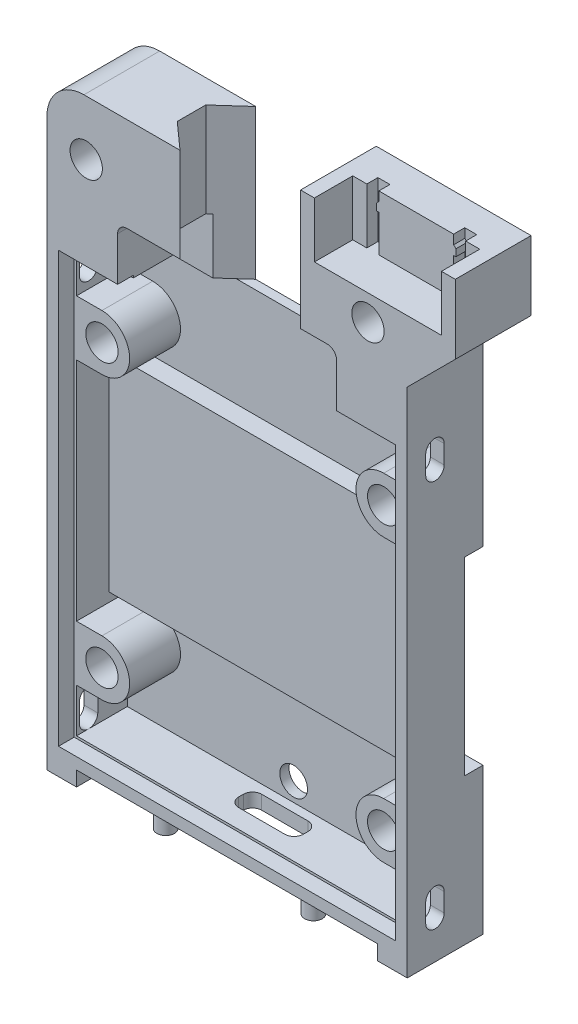
SolidWorks part; units mm, degrees
ref_plane "Front Plane" through (0, 0, 0) normal (0, 0, 1) x (1, 0, 0)
ref_plane "Top Plane" through (0, 0, 0) normal (0, 1, 0) x (1, 0, 0)
ref_plane "Right Plane" through (0, 0, 0) normal (1, 0, 0) x (0, 0, -1)
sketch "Sketch1" plane through (0, 0, 0) normal (0, 0, 1) x (1, 0, 0)
  line L0 (15.25, -20.35) -> (18, -20.35)
  line L1 (-19.5, -32.6) -> (19.5, -32.6)
  line L2 (-19.5, -32.6) -> (-19.5, 31.1)
  line L3 (-19.5, 31.1) -> (19.5, 31.1)
  line L4 (19.5, -32.6) -> (19.5, 31.1)
  line L5 (-15.25, -20.35) -> (-18, -20.35)
  line L6 (15.25, -26.35) -> (18, -26.35)
  line L7 (6.95, 31.1) -> (-15.5, 31.1) construction
  line L8 (-18, -31.1) -> (-18, 29.6)
  line L9 (-18, 29.6) -> (18, 29.6)
  line L10 (18, -31.1) -> (18, 29.6)
  line L11 (-18, -31.1) -> (18, -31.1)
  line L12 (-18, 14.9) -> (18, 14.9)
  line L13 (7.85, 14.9) -> (-4.95, 14.9) construction
  line L14 (-15.25, 4.15) -> (-18, 4.15)
  line L15 (-15.25, 10.15) -> (-18, 10.15)
  line L16 (15.25, 10.15) -> (18, 10.15)
  line L17 (15.25, 4.15) -> (18, 4.15)
  line L18 (-15.25, -26.35) -> (-18, -26.35)
  line L19 (19.5, -34.2) -> (19.5, -18.35) construction
  line L20 (-19.5, -34.2) -> (-19.5, -18.35) construction
  line L21 (15.3, -32.6) -> (-15.3, -32.6) construction
  line L22 (0, 31.1) -> (0, -32.6) construction
  line L23 (9.45, 26.9) -> (24.7, 26.9)
  line L24 (9.45, 26.9) -> (9.45, 33.9)
  line L25 (9.45, 33.9) -> (24.7, 33.9)
  line L26 (24.7, 26.9) -> (24.7, 33.9)
  line L27 (18, 29.6) -> (19.5, 31.1) construction
  line L28 (18.75, 30.35) -> (0, 30.35) construction
  line L29 (9.45, 26.9) -> (7.95, 26.9) construction
  line L30 (-7.95, 31.1) -> (7.95, 31.1)
  line L31 (-7.95, 31.1) -> (-7.95, 29.6)
  line L32 (-7.95, 29.6) -> (7.95, 29.6)
  line L33 (7.95, 31.1) -> (7.95, 29.6)
  line L34 (-7.95, 31.1) -> (7.95, 29.6) construction
  line L35 (-7.95, 29.6) -> (7.95, 31.1) construction
  line L36 (7.95, 26.9) -> (7.95, 29.6) construction
  line L37 (18, 29.6) -> (19.5, 29.6) construction
  line L38 (24.7, 26.4) -> (19.5, 21.2)
  line L39 (9.45, 33.9) -> (7.95, 33.9)
  line L40 (23.2, 33.9) -> (23.2, 26.9)
  line L41 (7.95, 33.9) -> (7.95, 31.1)
  line L42 (24.7, 30.4) -> (23.2, 30.4) construction
  line L43 (24.7, 26.9) -> (19.5, 26.9)
  line L44 (24.7, 26.9) -> (24.7, 26.4)
  line L45 (24.7, 26.4) -> (19.5, 26.4)
  line L46 (19.5, 26.9) -> (19.5, 26.4)
  circle A0 centre (15.25, -23.35) radius 1.75
  arc A1 (-15.5, 31.1) -> (-19.5, 27.1) centre (-15.5, 27.1) ccw construction
  circle A2 centre (15.25, -23.35) radius 3
  arc A3 (-15.5, 31.1) -> (-19.5, 27.1) centre (-15.5, 27.1) ccw
  arc A4 (-15.5, 29.6) -> (-18, 27.1) centre (-15.5, 27.1) ccw
  circle A6 centre (-15.25, -23.35) radius 1.75
  circle A7 centre (-15.25, -23.35) radius 1.75
  circle A8 centre (-15.25, 7.15) radius 1.75
  circle A9 centre (15.25, 7.15) radius 1.75
  circle A10 centre (15.25, 25.15) radius 1.75
  circle A11 centre (-15.25, 25.15) radius 1.75
  circle A12 centre (-15.25, -23.35) radius 3
  circle A13 centre (-15.25, -23.35) radius 3
  circle A14 centre (15.25, 7.15) radius 3
  circle A15 centre (-15.25, 7.15) radius 3
  dimension "D2" = 1.5
  dimension "D4" = 6
  dimension "D3" = 3.5
  dimension "D5" = 13.75
  dimension "D6" = 15.9
  dimension "D7" = 7
  dimension "D8" = 45
  dimension "D9" = 0.5
  dimension "D1" = 1.5
extrude "Base shape" add sketch "Sketch1" along normal up to surface (8.2 mm away) contours A15 L8 L9 L31 L3 A3 L2 L1 L4 L23 L10 A14 A2 L11 A12 | A12 L8 L18 | A12 L8 A6 | L8 A12 | A12 L5 L8 | A15 L8 L14 | A15 L8 A8 | L8 A15 | A15 L15 L8 | L23 A10 L24 L9 A4 L8 L12 L10 A11 | A4 L9 L8 | L33 L3 L31 L9 | L3 L33 L9 L24 | L24 L9 L10 L23 L4 L3 | L24 L23 L10 L9 | A14 L10 L16 | L10 A14 A9 | A14 L17 L10 | L10 A14 | L10 A2 L6 | A2 L10 A0 | L0 A2 L10 | A2 L10 | L40 L25 L24 L3 L4 L23 | L25 L40 L23 L26 | L38 L45 L4 | L45 L44 L23 L4 | L39 L41 L3 L24 region at (16.8481, -20.9099, 0) region at (17.3601, -20.8437, 0) region at (18.7469, -8.1, 0) region at (17.3601, -25.8563, 0) region at (18.1004, -23.35, 0) region at (17.3601, 4.6437, 0) region at (16.8481, 4.7099, 0) region at (18.1004, 7.15, 0) region at (17.3601, 9.6563, 0) region at (-17.3601, -25.8563, 0) region at (-0.6044, 21.831, 0) region at (-18.1004, -23.35, 0) region at (-17.9169, -23.35, 0) region at (13.725, 28.25, 0) region at (15.3803, 29.9053, 0) region at (-17.3601, -20.8437, 0) region at (22.1, 26.65, 0) region at (17.77, 31.4935, 0) region at (-17.3601, 9.6563, 0) region at (-17.4416, 29.0416, 0) region at (8.7, 30.35, 0) region at (21.2333, 24.6667, 0) region at (23.95, 30.4, 0) region at (-16.8481, 9.5901, 0) region at (-18.1004, 7.15, 0) region at (-17.3601, 4.6437, 0) region at (0, 30.35, 0) region at (8.7, 32.5, 0)
sketch "Sketch3" plane through (19.5, 0, 0) normal (1, 0, 0) x (0, 0, -1)
  line L1 (0, -18.35) -> (-2, -18.35)
  line L2 (0, -18.35) -> (0, 2.15)
  line L3 (0, 2.15) -> (-2, 2.15)
  line L4 (-2, -18.35) -> (-2, 2.15)
  line L5 (0, -18.35) -> (1.75, -18.35) construction
  line L6 (0, 2.15) -> (1.75, 2.15) construction
  line L7 (0, -32.6) -> (0, 21.2) construction
  dimension "D1" = 2
extrude "Strap cut" cut sketch "Sketch3" against normal through all
sketch "Sketch4" plane through (0, 31.1, 0) normal (0, 1, 0) x (1, 0, 0)
  line L2 (7.95, 0) -> (-5.0998, 0)
  line L4 (-15.5, 0) -> (7.95, 0) construction
  line L5 (-15.5, -8.2) -> (7.95, -8.2) construction
  line L6 (7.95, -8.2) -> (-5.0998, -8.2)
  line L12 (7.95, -8.3) -> (7.95, 0.1)
  line L13 (7.95, 0.1) -> (-4.9883, 0.1)
  line L14 (-4.9883, 0.1) -> (-7.95, -2.5553)
  line L15 (-7.95, -2.5553) -> (-7.95, -5.6447)
  line L16 (-7.95, -5.6447) -> (-4.9883, -8.3)
  line L17 (-4.9883, -8.3) -> (7.95, -8.3)
  line L18 (7.95, -8.3) -> (7.95, 0.1)
  line L19 (7.95, 0.1) -> (-4.9883, 0.1)
  line L20 (-4.9883, 0.1) -> (-7.95, -2.5553)
  line L21 (-7.95, -2.5553) -> (-7.95, -5.6447)
  line L22 (-7.95, -5.6447) -> (-4.9883, -8.3)
  line L23 (-4.9883, -8.3) -> (7.95, -8.3)
  dimension "D1" = 0.1
extrude "XT60 cut" cut sketch "Sketch4" against normal up to next contours L21 L22 L18 L20 region at (0.4142, 31.1, 4.1)
sketch "Sketch5" plane through (19.5, 0, 0) normal (1, 0, 0) x (0, 0, -1)
  line L1 (-8.2, -32.6) -> (-8.2, 21.2) construction
  line L2 (-6.2, -31.1) -> (-4.2, -31.1)
  line L3 (-6.2, -31.1) -> (-6.2, -27.1)
  line L4 (-6.2, -27.1) -> (-4.2, -27.1)
  line L5 (-4.2, -31.1) -> (-4.2, -27.1)
  line L6 (-8.2, -31.1) -> (0, -31.1) construction
  line L7 (-8.2, 14.9) -> (0, 14.9) construction
  line L8 (-6.2, 14.9) -> (-4.2, 14.9)
  line L9 (-6.2, 14.9) -> (-6.2, 10.9)
  line L10 (-6.2, 10.9) -> (-4.2, 10.9)
  line L11 (-4.2, 14.9) -> (-4.2, 10.9)
  line L14 (-5.2, -27.1) -> (-5.2, -31.1) construction
  line L15 (-5.2, 14.9) -> (-5.2, 10.9) construction
  circle A0 centre (-5.2, -28.1) radius 1
  circle A1 centre (-5.2, -30.1) radius 1
  circle A2 centre (-5.2, 13.9) radius 1
  circle A3 centre (-5.2, 11.9) radius 1
  point P20 (-5.2, -29.1)
  point P31 (-5.2, 12.9)
  dimension "D3" = 4
  dimension "D1" = 2
  dimension "D2" = 2
extrude "Power wires cut" cut sketch "Sketch5" against normal through all contours A2 | A3 | A3 A2 L9 | A3 L11 A2 | A1 | A0 | A1 L5 A0 | A1 A0 L3 region at (19.5, -30.1, 5.2) region at (19.5, -29.1, 5.9766) region at (19.5, -29.1, 4.4234) region at (19.5, -28.1, 5.2) region at (19.5, 13.9, 5.2) region at (19.5, 12.9, 5.9766) region at (19.5, 12.9, 4.4234) region at (19.5, 11.9, 5.2)
sketch "Sketch6" plane through (0, 0, 8.2) normal (0, 0, 1) x (1, 0, 0)
  line L0 (8.85, 14.9) -> (10.85, 14.9) construction
  line L1 (-11.85, 19.9) -> (11.85, 19.9)
  line L2 (-11.85, 19.9) -> (-11.85, 14.9)
  line L3 (-11.85, 14.9) -> (11.85, 14.9)
  line L4 (11.85, 19.9) -> (11.85, 14.9)
  line L5 (-10.85, 20.9) -> (10.85, 20.9)
  arc A0 (11.85, 19.9) -> (10.85, 20.9) centre (10.85, 19.9) ccw construction
  arc A1 (-10.85, 20.9) -> (-11.85, 19.9) centre (-10.85, 19.9) ccw construction
  arc A2 (11.85, 19.9) -> (10.85, 20.9) centre (10.85, 19.9) ccw
  arc A3 (-10.85, 20.9) -> (-11.85, 19.9) centre (-10.85, 19.9) ccw
  line M1 (7.95, 33.9) -> (7.95, 14.9)
  line M15 (-5.0998, 14.9) -> (-5.0998, 31.1)
  line M118 (7.95, 14.9) -> (18, 14.9)
  line M134 (-18, 14.9) -> (-5.0998, 14.9)
extrude "IO wires cut" cut sketch "Sketch6" against normal blind 6 contours L5 A3 L1 M15 | L1 L2 M134 M15 | L5 L1 M15 M1 | L3 L1 M15 M1 | L1 A2 L5 M1 | L4 L1 M1 M118 region at (-8.3714, 20.3909, 8.2) region at (-8.4749, 17.4, 8.2) region at (1.4251, 20.4, 8.2) region at (1.4251, 17.4, 8.2) region at (9.7995, 20.3839, 8.2) region at (9.9, 17.4, 8.2)
sketch "Sketch7" plane through (-18, 0, 0) normal (1, 0, 0) x (0, 0, -1)
  line L6 (0, -18.35) -> (0, -20.35)
  line L7 (-2, -18.35) -> (0, -18.35)
  line L8 (-2, 2.15) -> (-2, -18.35)
  line L9 (0, 2.15) -> (-2, 2.15)
  line L12 (0, 3.15) -> (-3, 3.15)
  line L13 (-3, 3.15) -> (-3, -19.35)
  line L14 (-3, -19.35) -> (-1, -19.35)
  line L15 (-1, -19.35) -> (-1, -20.35)
  line L16 (-1, -20.35) -> (0, -20.35)
  line L17 (0, 3.15) -> (-1, 3.15)
  line L19 (0, -31.1) -> (-1, -31.1)
  line L22 (0, -31.1) -> (0, -20.35)
  line L23 (0, -20.35) -> (-1, -20.35)
  line L24 (-1, -31.1) -> (-1, -20.35)
  line L25 (0, 3.15) -> (0, 14.9)
  line L26 (0, 14.9) -> (-1, 14.9)
  line L27 (-1, 3.15) -> (-1, 14.9)
  line L28 (-5.2, 14.9) -> (0, 14.9) construction
  line L31 (0, -20.35) -> (0, -18.35) construction
  line L32 (0, 2.15) -> (-2, 2.15) construction
  line M48 (0, -20.35) -> (0, -18.35)
  line M49 (0, -18.35) -> (-2, -18.35)
  line M50 (-2, -18.35) -> (-2, 2.15)
  line M51 (-2, 2.15) -> (0, 2.15)
  line M52 (0, 2.15) -> (0, 4.15)
  line M53 (0, 4.15) -> (-8.2, 4.15)
  line M55 (-8.2, -20.35) -> (0, -20.35)
  dimension "D1" = 1
extrude "Bottom" add sketch "Sketch7" along normal up to surface (36 mm away) contours L27 L25 L26 M53 | L27 L12 M52 M53 | L14 L15 L12 L13 M55 M48 M49 M50 M51 M52 | L24 L19 L22 M55 region at (-18, -8.5273, 2.2091) region at (-18, -25.725, 0.5) region at (-18, 3.65, 0.5) region at (-18, 9.525, 0.5) up to face at (18, -8.1, 2.55)
sketch "Sketch9" plane through (0, 0, 0) normal (0, 0, -1) x (-1, 0, 0)
  circle A0 centre (15.25, -23.35) radius 1.75 construction
  circle A1 centre (-15.25, 7.15) radius 1.75 construction
  circle A2 centre (15.25, 7.15) radius 1.75 construction
  circle A3 centre (15.25, -23.35) radius 1.75 construction
  circle A4 centre (15.25, -23.35) radius 1.75
  circle A5 centre (-15.25, 7.15) radius 1.75
  circle A6 centre (15.25, 7.15) radius 1.75
  circle A7 centre (15.25, -23.35) radius 1.75
  circle A8 centre (-15.25, -23.35) radius 1.75 construction
  circle A9 centre (-15.25, -23.35) radius 1.75
extrude "Bottom holes" cut sketch "Sketch9" against normal up to next contours A5 | A6 | A4 | A9 region at (-15.25, -23.35, 0) region at (15.25, 7.15, 0) region at (-15.25, 7.15, 0) region at (15.25, -23.35, 0)
sketch "Sketch8" plane through (0, 0, 8.2) normal (0, 0, 1) x (1, 0, 0)
  line L0 (-6.2152, 14.9) -> (-18, 14.9) construction
  line L1 (-18.25, 15.15) -> (18.25, 15.15)
  line L2 (-18.25, 15.15) -> (-18.25, -31.35)
  line L3 (-18.25, -31.35) -> (18.25, -31.35)
  line L4 (18.25, 15.15) -> (18.25, -31.35)
  line L5 (-18, 14.9) -> (-18.25, 14.9) construction
  line L6 (-18, 14.9) -> (-18, 15.15) construction
  line L7 (18, 14.9) -> (18.25, 14.9) construction
  line L8 (-18, -31.1) -> (-18, -31.35) construction
  dimension "D1" = 0.25
extrude "PCB cut" cut sketch "Sketch8" against normal blind 1.7
sketch "Sketch11" plane through (0, -32.6, 0) normal (0, -1, 0) x (1, 0, 0)
  line L0 (19.5, 8.2) -> (19.5, 0) construction
  line L1 (-19.5, 8.2) -> (19.5, 8.2)
  line L2 (-19.5, 8.2) -> (-19.5, -1.8)
  line L3 (-19.5, -1.8) -> (19.5, -1.8)
  line L4 (19.5, 8.2) -> (19.5, -1.8)
  line L5 (-19.5, 3.2) -> (19.5, 3.2) construction
  line L6 (0, -1.8) -> (0, 8.2) construction
  line L8 (-2.5, 4.45) -> (2.5, 4.45)
  line L9 (-3.5, 3.45) -> (-3.5, 2.95)
  line L10 (-2.5, 1.95) -> (2.5, 1.95)
  line L11 (3.5, 3.45) -> (3.5, 2.95)
  line L12 (-3.5, 4.45) -> (3.5, 1.95) construction
  line L13 (-3.5, 1.95) -> (3.5, 4.45) construction
  arc A0 (2.5, 4.45) -> (3.5, 3.45) centre (2.5, 3.45) cw
  arc A1 (2.5, 1.95) -> (3.5, 2.95) centre (2.5, 2.95) ccw
  arc A2 (-3.5, 2.95) -> (-2.5, 1.95) centre (-2.5, 2.95) ccw
  arc A3 (-2.5, 4.45) -> (-3.5, 3.45) centre (-2.5, 3.45) ccw
  point P11 (0, 3.2)
  dimension "D4" = 1
  dimension "D1" = 10
  dimension "D2" = 7
  dimension "D3" = 2.5
extrude "Ledbar wires cut" cut sketch "Sketch11" against normal up to next contours L8 A3 L9 A2 L10 A1 L11 A0 region at (0, -32.6, 3.2)
sketch "Sketch13" plane through (0, -32.6, 0) normal (0, -1, 0) x (1, 0, 0)
  line L0 (-19.5, 8.2) -> (19.5, 8.2) construction
  line L1 (19.5, 0) -> (16.3, 0)
  line L2 (19.5, 0) -> (19.5, 8.2)
  line L3 (19.5, 8.2) -> (16.3, 8.2)
  line L4 (16.3, 0) -> (16.3, 8.2)
  line L5 (16.1, -1.8) -> (16.1, 8.2) construction
  line L6 (0, 8.2) -> (0, 0) construction
  line L7 (-19.5, 0) -> (-16.3, 0)
  line L8 (-19.5, 0) -> (-19.5, 8.2)
  line L9 (-19.5, 8.2) -> (-16.3, 8.2)
  line L10 (-16.3, 0) -> (-16.3, 8.2)
  dimension "D1" = 0.2
extrude "Ledbar sides" add sketch "Sketch13" along normal blind 1.6
sketch "Sketch14" plane through (0, -32.6, 0) normal (0, -1, 0) x (1, 0, 0)
  circle A0 centre (8, 6.85) radius 0.95
  circle A1 centre (-8, 6.85) radius 0.95
  dimension "D1" = 1.9
extrude "Ledbar mounts" add sketch "Sketch14" along normal blind 2
sketch "Sketch16" plane through (0, 33.9, 0) normal (0, 1, 0) x (1, 0, 0)
  line L0 (7.95, -6.125) -> (24.7, -6.125) construction
  line L1 (7.95, -8.2) -> (24.7, -8.2) construction
  line L2 (21.675, -2.85) -> (20.375, -2.85)
  line L3 (20.375, -4.05) -> (20.375, -2.85)
  line L4 (9.45, -4.05) -> (23.2, -4.05)
  line L5 (9.45, -4.05) -> (9.45, -8.2)
  line L6 (9.45, -8.2) -> (23.2, -8.2)
  line L7 (23.2, -4.05) -> (23.2, -8.2)
  line L8 (9.45, -4.05) -> (23.2, -8.2) construction
  line L9 (9.45, -8.2) -> (23.2, -4.05) construction
  line L10 (24.7, -8.2) -> (24.7, 0) construction
  line L11 (7.95, -8.2) -> (7.95, 0) construction
  line L12 (16.325, -8.2) -> (16.325, -4.05) construction
  line L13 (11.625, -2.85) -> (11.625, -4.05) construction
  line L14 (10.975, -4.05) -> (12.275, -4.05)
  line L15 (10.975, -4.05) -> (10.975, -2.85)
  line L16 (10.975, -2.85) -> (12.275, -2.85)
  line L17 (12.275, -4.05) -> (12.275, -2.85)
  line L18 (10.975, -2.85) -> (10.975, -8.2) construction
  line L19 (21.675, -4.05) -> (21.675, -2.85)
  point P6 (16.325, -6.125)
  dimension "D1" = 13.75
  dimension "D2" = 4.15
  dimension "D3" = 1.3
  dimension "D4" = 1.2
  dimension "D5" = 4.7
extrude "Balance plug cut" cut sketch "Sketch16" against normal blind 6 contours L7 L4 L5 L6 | L4 L17 L16 L15 | L4 L19 L2 L3 region at (21.025, 33.9, 3.45) region at (16.325, 33.9, 6.125) region at (11.625, 33.9, 3.45)
sketch "Sketch17" plane through (0, 0, 2.85) normal (0, 0, 1) x (1, 0, 0)
  line L0 (16.325, 33.9) -> (16.325, 27.9) construction
  line L1 (12.275, 33.9) -> (20.375, 33.9) construction
  line L2 (12.275, 27.9) -> (20.375, 27.9) construction
  line L3 (12.275, 27.9) -> (12.275, 33.9) construction
  line L4 (12.025, 32.9) -> (20.625, 32.9)
  line L5 (12.025, 32.9) -> (12.025, 31.9)
  line L6 (12.025, 31.9) -> (20.625, 31.9)
  line L7 (20.625, 32.9) -> (20.625, 31.9)
  line L8 (12.025, 32.9) -> (20.625, 31.9) construction
  line L9 (12.025, 31.9) -> (20.625, 32.9) construction
  line L10 (12.025, 32.65) -> (12.275, 32.9)
  line L11 (20.625, 32.65) -> (20.375, 32.9)
  point P6 (16.325, 32.4)
  line M7 (20.375, 33.9) -> (20.375, 27.9)
  dimension "D1" = 0.25
  dimension "D2" = 1
  dimension "D3" = 1
  dimension "D4" = 45
extrude "Balance plug locks" add sketch "Sketch17" along normal up to surface (1.2 mm away) contours L10 L5 L6 L4 M7 | L7 L11 L6 M7 region at (16.2154, 32.3984, 2.85) region at (20.494, 32.3405, 2.85) up to face at (22.4375, 30.9, 4.05)
sketch "Sketch18" plane through (0, 0, 0) normal (0, 0, -1) x (-1, 0, 0)
  line L0 (0, -32.6) -> (0, -18.35) construction
  line L1 (16.3, -32.6) -> (-16.3, -32.6) construction
  line L2 (19.5, -18.35) -> (-19.5, -18.35) construction
  line L3 (-19.5, -30.6) -> (19.5, -30.6) construction
  line L4 (-19.5, -34.2) -> (-19.5, -18.35) construction
  line L5 (19.5, -34.2) -> (19.5, -18.35) construction
  circle A0 centre (0, -29.1) radius 1.5
  dimension "D2" = 3
  dimension "D1" = 2
extrude "PDB removal hole" cut sketch "Sketch18" against normal up to next
sketch "Sketch10" [suppressed] plane through (0, 0, 2) normal (0, 0, -1) x (-1, 0, 0)
  line L0 (0, 2.15) -> (0, -18.35) construction
  line L1 (19.5, 2.15) -> (-19.5, 2.15) construction
  line L2 (19.5, -18.35) -> (-19.5, -18.35) construction
  line L3 (19.5, 2.15) -> (19.5, -18.35) construction
  line L4 (-19.5, 1.15) -> (19.5, 1.15)
  line L5 (-19.5, 1.15) -> (-19.5, 0.65)
  line L6 (-19.5, 0.65) -> (19.5, 0.65)
  line L7 (19.5, 1.15) -> (19.5, 0.65)
  line L8 (-19.5, 1.15) -> (19.5, 0.65) construction
  line L9 (-19.5, 0.65) -> (19.5, 1.15) construction
  line L10 (-19.5, 2.15) -> (19.5, 2.15) construction
  line L11 (-19.5, -1.35) -> (19.5, -1.35)
  line L12 (19.5, -0.85) -> (19.5, -1.35)
  line L13 (-19.5, -0.85) -> (19.5, -0.85)
  line L14 (-19.5, -0.85) -> (-19.5, -1.35)
  line L15 (-19.5, -3.35) -> (19.5, -3.35)
  line L16 (19.5, -2.85) -> (19.5, -3.35)
  line L17 (-19.5, -2.85) -> (19.5, -2.85)
  line L18 (-19.5, -2.85) -> (-19.5, -3.35)
  line L19 (-19.5, -5.35) -> (19.5, -5.35)
  line L20 (19.5, -4.85) -> (19.5, -5.35)
  line L21 (-19.5, -4.85) -> (19.5, -4.85)
  line L22 (-19.5, -4.85) -> (-19.5, -5.35)
  line L23 (-19.5, -7.35) -> (19.5, -7.35)
  line L24 (19.5, -6.85) -> (19.5, -7.35)
  line L25 (-19.5, -6.85) -> (19.5, -6.85)
  line L26 (-19.5, -6.85) -> (-19.5, -7.35)
  line L27 (-19.5, -9.35) -> (19.5, -9.35)
  line L28 (19.5, -8.85) -> (19.5, -9.35)
  line L29 (-19.5, -8.85) -> (19.5, -8.85)
  line L30 (-19.5, -8.85) -> (-19.5, -9.35)
  line L31 (-19.5, -11.35) -> (19.5, -11.35)
  line L32 (19.5, -10.85) -> (19.5, -11.35)
  line L33 (-19.5, -10.85) -> (19.5, -10.85)
  line L34 (-19.5, -10.85) -> (-19.5, -11.35)
  line L35 (-19.5, -13.35) -> (19.5, -13.35)
  line L36 (19.5, -12.85) -> (19.5, -13.35)
  line L37 (-19.5, -12.85) -> (19.5, -12.85)
  line L38 (-19.5, -12.85) -> (-19.5, -13.35)
  line L39 (-19.5, -15.35) -> (19.5, -15.35)
  line L40 (19.5, -14.85) -> (19.5, -15.35)
  line L41 (-19.5, -14.85) -> (19.5, -14.85)
  line L42 (-19.5, -14.85) -> (-19.5, -15.35)
  line L43 (-19.5, -17.35) -> (19.5, -17.35)
  line L44 (19.5, -16.85) -> (19.5, -17.35)
  line L45 (-19.5, -16.85) -> (19.5, -16.85)
  line L46 (-19.5, -16.85) -> (-19.5, -17.35)
  point P6 (0, 0.9)
  dimension "D1" = 1
  dimension "D2" = 0.5
  dimension "D4" = 2
  dimension "D3" = 10
extrude "3D print ribs" [suppressed] add sketch "Sketch10" along normal up to surface (2 mm away) up to face at (-17, 7.15, 0)
sketch "Sketch15" [suppressed] plane through (0, 0, 0) normal (0, 0, -1) x (-1, 0, 0)
  line L0 (-8, -34.6) -> (-8, -32.6) construction
  line L1 (-8.95, -34.6) -> (-7.05, -34.6) construction
  line L2 (-8.95, -32.6) -> (-7.05, -32.6) construction
  line L3 (0, -32.6) -> (0, 14.9) construction
  line L4 (-8.25, -34.6) -> (-7.75, -34.6)
  line L5 (-8.25, -34.6) -> (-8.25, -32.6)
  line L6 (-8.25, -32.6) -> (-7.75, -32.6)
  line L7 (-7.75, -34.6) -> (-7.75, -32.6)
  line L8 (-8.25, -34.6) -> (-7.75, -32.6) construction
  line L9 (-8.25, -32.6) -> (-7.75, -34.6) construction
  line L10 (16.3, -32.6) -> (-16.3, -32.6) construction
  line L11 (-7.95, 14.9) -> (5.0998, 14.9) construction
  line L12 (8.25, -32.6) -> (7.75, -32.6)
  line L13 (7.75, -34.6) -> (7.75, -32.6)
  line L14 (8.25, -34.6) -> (7.75, -34.6)
  line L15 (8.25, -34.6) -> (8.25, -32.6)
  point P6 (-8, -33.6)
  dimension "D1" = 0.5
extrude "3D print led supports" [suppressed] add sketch "Sketch15" against normal up to next
